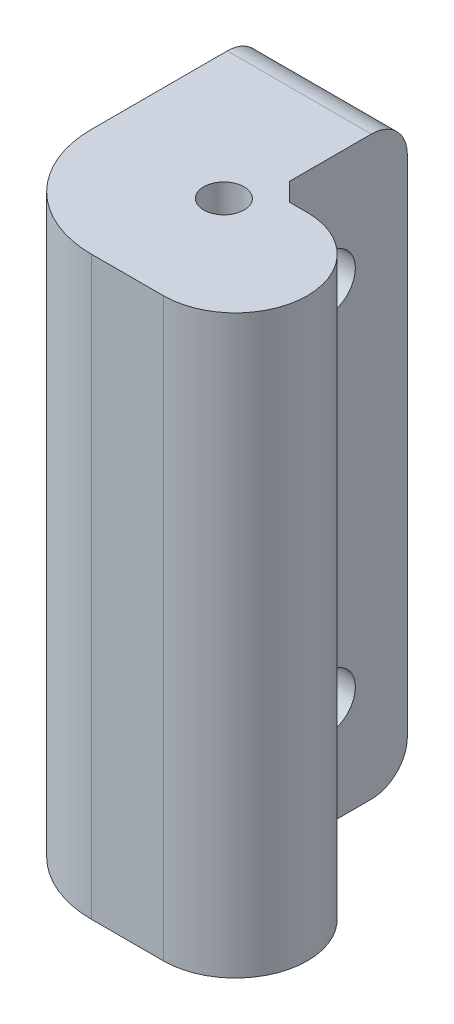
SolidWorks part; units mm, degrees
material "Polycarbonate"
ref_plane "Front Plane" through (0, 0, 0) normal (0, 0, 1) x (1, 0, 0)
ref_plane "Top Plane" through (0, 0, 0) normal (0, 1, 0) x (1, 0, 0)
ref_plane "Right Plane" through (0, 0, 0) normal (1, 0, 0) x (0, 0, -1)
sketch "Sketch1" plane through (0, 0, 0) normal (0, 1, 0) x (1, 0, 0)
  line L0 (0, 0) -> (0, 5.9944)
  line L1 (0, 5.9944) -> (-6.35, 5.9944)
  line L2 (-6.35, 5.9944) -> (-6.35, -6.35)
  line L3 (-6.35, -6.35) -> (4.7625, -6.35)
  line L4 (4.7625, -6.35) -> (4.7625, 0)
  line L5 (4.7625, 0) -> (0, 0)
  dimension "D1" = 5.9944
  dimension "D2" = 6.35
  dimension "D3" = 4.7625
  dimension "D4" = 6.35
extrude "Boss-Extrude1" add sketch "Sketch1" along normal blind 25.4
chamfer "Chamfer1" distance 0.7937 angle 45 1 edges at (0, 12.7, 0)
hole_wizard "M2 Clearance Hole1" positions "Sketch3" profile "Sketch4" hole size "M2" standard "ANSI Metric" end condition up to next
sketch "Sketch3" plane through (0, 0, 0) normal (1, 0, 0) x (0, 0, -1)
  line L0 (2.5, 20.6391) -> (2.5, 4.6391) construction
  line L1 (0.7937, 25.4) -> (5.9944, 25.4) construction
  line L2 (5.9944, 25.4) -> (5.9944, 0) construction
  point P0 (2.5, 20.6391)
  point P3 (2.5, 4.6391)
  dimension "D1" = 16
  dimension "D2" = 4.7609
  dimension "D3" = 3.4944
sketch "Sketch4" plane through (0, 20.6391, -2.5) normal (0, 1, 0) x (0, 0, -1)
  line L0 (0, 0) -> (0, 6.35)
  line L1 (0, 6.35) -> (1.2, 6.35)
  line L2 (1.2, 6.35) -> (1.2, 0)
  line L5 (1.2, 0) -> (0, 0)
  line L11 (0, -6.35) -> (0, 107.95) construction
  dimension "Thru Hole Dia." = 2.4
  dimension "Thru Hole Depth" = 6.35
fillet "Fillet1" radius 4.7625 1 edges at (-6.35, 12.7, 6.35)
fillet "Fillet3" 2 edges at (4.7625, 12.7, 6.35) (4.7625, 12.7, 0) type full round first side face at (1.5875, 12.7, 6.35) second side face at (2.7781, 12.7, 0) middle face at (4.7625, 12.7, 3.175)
fillet "Fillet4" radius 1.5875 2 edges at (-3.175, 25.4, -5.9944) (-3.175, 0, -5.9944)
ref_plane "Plane1" through (4.7625, 0, 0) normal (1, 0, 0) x (0, 0, -1)
sketch "Sketch5" plane through (0, 0, 0) normal (0, -1, 0) x (-1, 0, 0)
  line L0 (0, 0.7937) -> (0, 4.4069) construction
  line L4 (-1.5875, 0) -> (-0.7937, 0) construction
  circle A0 centre (0.7937, -1.303) radius 0.7938 construction
  circle A1 centre (0.7937, -1.303) radius 0.889
  dimension "D2" = 1.303
  dimension "D1" = 1.5875
  dimension "D3" = 1.778
extrude "Cut-Extrude2" cut sketch "Sketch5" against normal through all
